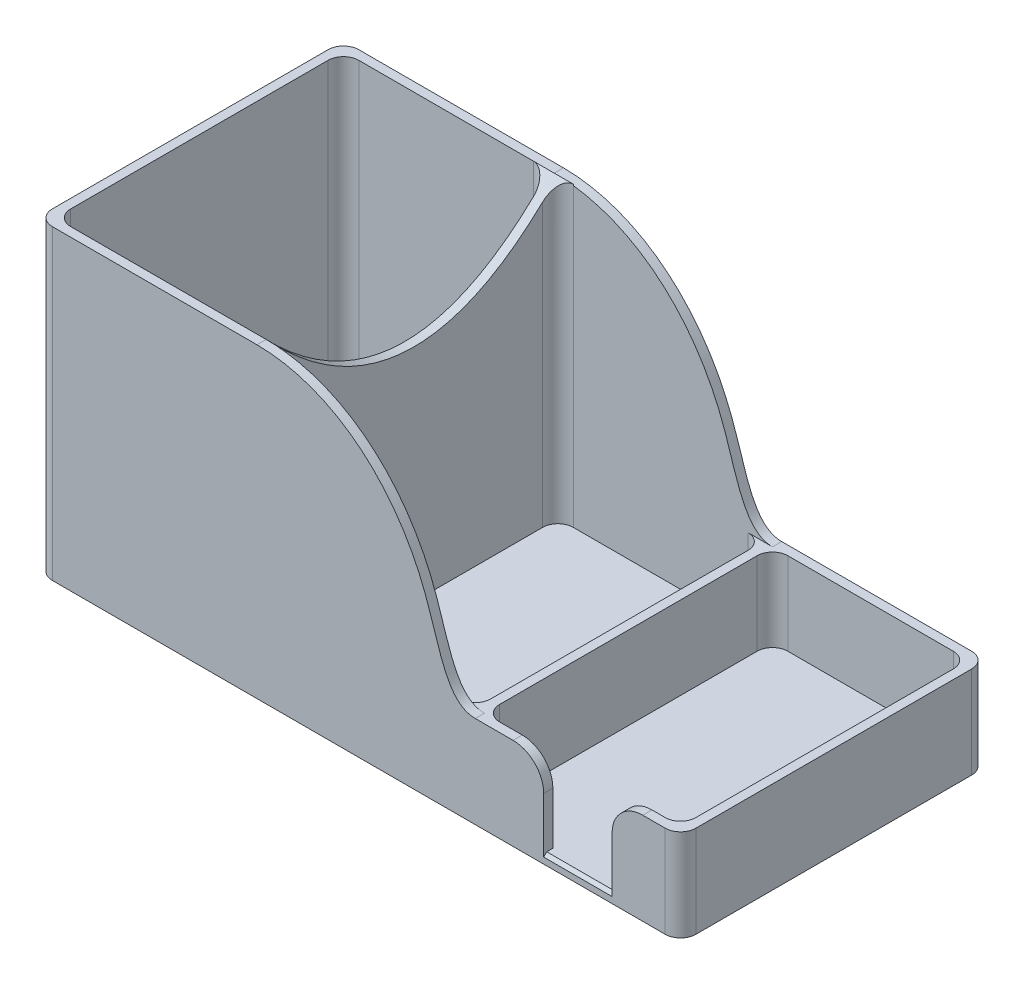
SolidWorks part; units mm, degrees
ref_plane "Спереди" through (0, 0, 0) normal (0, 0, 1) x (1, 0, 0)
ref_plane "Сверху" through (0, 0, 0) normal (0, 1, 0) x (1, 0, 0)
ref_plane "Справа" through (0, 0, 0) normal (1, 0, 0) x (0, 0, -1)
other "Configuration Table"
sketch "Эскиз1" plane through (0, 0, 0) normal (0, 1, 0) x (1, 0, 0)
  line L0 (-35, 50) -> (-35, -50)
  line L1 (-105, -50) -> (105, -50)
  line L2 (-105, -50) -> (-105, 50)
  line L3 (-105, 50) -> (105, 50)
  line L4 (105, -50) -> (105, 50)
  line L5 (35, 50) -> (35, -50)
  line L6 (-32, 50) -> (-32, -50)
  line L7 (-102, 47) -> (102, 47)
  line L8 (102, -47) -> (102, 47)
  line L9 (-102, -47) -> (102, -47)
  line L10 (-102, -47) -> (-102, 47)
  line L11 (38, 50) -> (38, -50)
  point P0 (0, 0)
  point P18 (-35, -47)
  point P19 (-32, -47)
  point P20 (-32, 47)
  point P21 (38, 47)
  point P22 (-35, 47)
  point P23 (35, 47)
  point P24 (38, -47)
  point P25 (35, -47)
  dimension "D1" = 210
  dimension "D2" = 100
  dimension "D3" = 50
  dimension "D4" = 105
  dimension "D5" = 70
  dimension "D6" = 70
  dimension "D7" = 70
  dimension "D8" = 3
extrude "Бобышка-Вытянуть1" add sketch "Эскиз1" along normal blind 3 contours L10 L9 L0 L7 | L11 L9 L5 L7 | L7 L6 L9 L8 region at (-68.5, 0, 0) region at (1.5, 0, 0) region at (70, 0, 0)
extrude "Бобышка-Вытянуть2" add sketch "Эскиз1<4>" along normal blind 100 contours L9 L10 L7 L0 L3 L2 L1 region at (-36.2207, 0, -48.5)
sketch "Эскиз1<4>" plane through (0, 0, 0) normal (0, 1, 0) x (1, 0, 0) same geometry as "Эскиз1"
extrude "Бобышка-Вытянуть3" add sketch "Эскиз1<5>" along normal blind 30 contours L3 L11 L7 L8 L9 L1 L4 region at (71.5, 0, -48.7963)
sketch "Эскиз1<5>" plane through (0, 0, 0) normal (0, 1, 0) x (1, 0, 0) same geometry as "Эскиз1"
extrude "Бобышка-Вытянуть4" add sketch "Эскиз1<6>" along normal blind 100 contours L11 L3 L5 L7 | L6 L7 L5 L3 | L0 L7 L6 L3 | L11 L9 L5 L1 | L9 L6 L1 L5 | L9 L0 L1 L6 region at (-33.5, 0, -48.5) region at (1.5, 0, -48.5) region at (-33.5, 0, 48.5) region at (36.5, 0, -48.5) region at (1.5, 0, 48.5) region at (36.5, 0, 48.5)
sketch "Эскиз1<6>" plane through (0, 0, 0) normal (0, 1, 0) x (1, 0, 0) same geometry as "Эскиз1"
ref_plane "Плоскость1" through (0, 0, 50) normal (0, 0, 1) x (1, 0, 0)
sketch "Эскиз2" plane through (0, 0, 50) normal (0, 0, 1) x (1, 0, 0)
  line L0 (-105, 100) -> (38, 100) construction
  line L1 (38, 30) -> (105, 30) construction
  line L2 (38, 100) -> (38, 30) construction
  line L3 (38, 100) -> (38, 30)
  line L4 (-105, 100) -> (38, 100)
  spline S0 degree 3 poles (-33.5, 100) (-9.9706, 100.0646) (21.2435, 77.0078) (28.6565, 30) (38, 30) knots 0 0 0 0 0.695263 1 1 1 1
  point P2 (0, 0)
  point P6 (-33.2168, 100)
  point P8 (0, 0)
extrude "Вырез-Вытянуть1" cut sketch "Эскиз2" against normal blind 100 contours L4 S0 L3 region at (21.9116, 76.4359, 50)
sketch "Эскиз3" plane through (0, 0, 50) normal (0, 0, 1) x (1, 0, 0)
  line L0 (105, 30) -> (105, 0) construction
  line L1 (38, 30) -> (105, 30) construction
  line L2 (105, 30) -> (105, 0)
  line L3 (38, 30) -> (105, 30)
  line L4 (-105, 0) -> (105, 0) construction
  line L5 (82.6667, 30) -> (60.3333, 30)
  line L6 (82.6667, 30) -> (82.6667, 0)
  line L7 (82.6667, 0) -> (60.3333, 0)
  line L8 (60.3333, 30) -> (60.3333, 0)
  line L9 (38, 30) -> (38, 0)
  dimension "D1" = 67
  dimension "D2" = 22.3333
  dimension "D3" = 22.3333
extrude "Вырез-Вытянуть2" cut sketch "Эскиз3" against normal blind 3 contours L3 L8 L7 L6 region at (71.5, 15, 50)
extrude "Бобышка-Вытянуть5" add sketch "Эскиз1<7>" along normal blind 3 contours L3 L11 L7 L8 L9 L1 L4 region at (71.5, 0, -48.7963)
sketch "Эскиз1<7>" plane through (0, 0, 0) normal (0, 1, 0) x (1, 0, 0) same geometry as "Эскиз1"
extrude "Бобышка-Вытянуть6" add sketch "Эскиз1<8>" along normal blind 30 contours L11 L7 L5 L9 region at (36.5, 0, 0)
sketch "Эскиз1<8>" plane through (0, 0, 0) normal (0, 1, 0) x (1, 0, 0) same geometry as "Эскиз1"
extrude "Бобышка-Вытянуть7" add sketch "Эскиз1<9>" along normal blind 100 contours L0 L9 L6 L7 region at (-33.5, 0, 0)
sketch "Эскиз1<9>" plane through (0, 0, 0) normal (0, 1, 0) x (1, 0, 0) same geometry as "Эскиз1"
ref_plane "Плоскость4" through (-32, 0, 0) normal (1, 0, 0) x (0, 0, -1)
sketch "Эскиз5" plane through (-32, 0, 0) normal (1, 0, 0) x (0, 0, -1)
  line L0 (47, 100) -> (-47, 100) construction
  line L1 (47, 100) -> (-47, 100)
  spline S0 degree 2 poles (-47, 100) (0, 50) (47, 100) knots 0 0 0 1 1 1
  point P2 (0, 100)
  point P3 (0, 0)
  dimension "D1" = 25
extrude "Вырез-Вытянуть3" cut sketch "Эскиз5" against normal blind 3
fillet "Скругление1" radius 5 4 edges at (105, 15, -50) (105, 15, 50) (-105, 50, -50) (-105, 50, 50)
fillet "Скругление2" radius 10 2 edges at (82.6667, 30, 48.5) (60.3333, 30, 48.5)
fillet "Скругление3" radius 5 12 edges at (38, 16.5, 47) (35, 16.5, 47) (38, 16.5, -47) (35, 16.5, -47) (-32, 51.4911, 47) (102, 16.5, 47) (102, 16.5, -47) (-32, 51.4911, -47) (-35, 51.5, 47) (-102, 51.5, 47) (-35, 51.5, -47) (-102, 51.5, -47)
chamfer "Фаска1" distance 1 angle 45 1 edges at (71.5, 3, 50)
